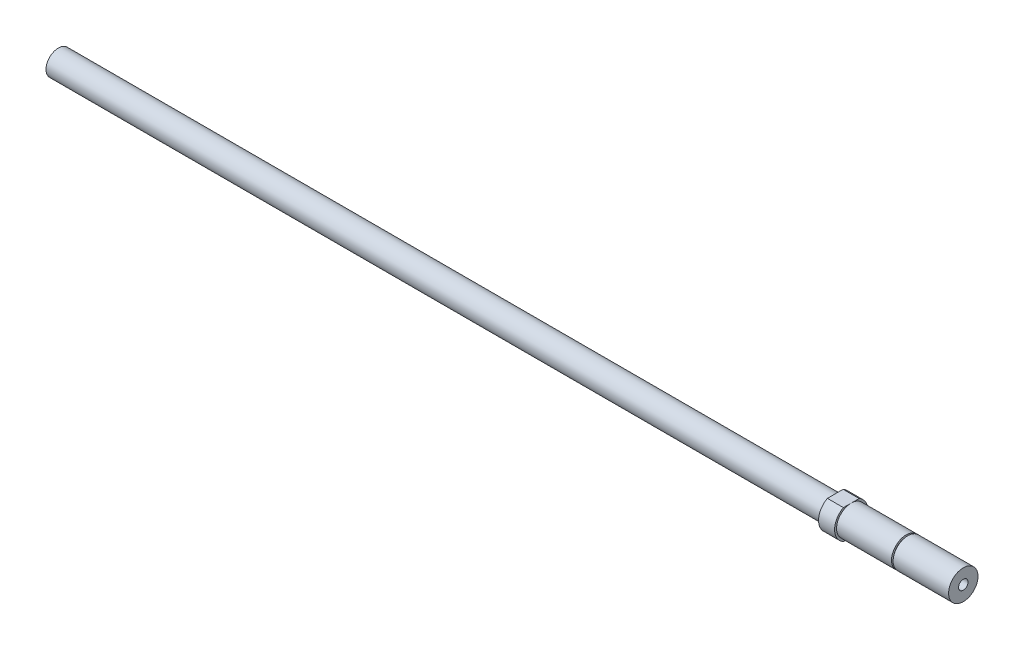
SolidWorks part; units mm, degrees
ref_plane "XY" through (0, 0, 0) normal (0, 0, 1) x (1, 0, 0)
ref_plane "XZ" through (0, 0, 0) normal (0, 1, 0) x (1, 0, 0)
ref_plane "YZ" through (0, 0, 0) normal (1, 0, 0) x (0, 0, -1)
ref_axis "X" through (-226.1616, 0, 0) along (1, 0, 0)
ref_axis "Y" through (0, -3.85, 0) along (0, 1, 0)
ref_axis "Z" through (0, 0, 4.3656) along (0, 0, -1)
sketch "Sketch1" plane through (0, 0, 0) normal (0, 0, 1) x (1, 0, 0)
  line L0 (0, 0) -> (-215.392, 0)
  line L1 (-215.392, 0) -> (-215.392, 2.95)
  line L2 (-215.392, 2.95) -> (-30.48, 2.95)
  line L3 (-30.48, 2.95) -> (-30.48, 3.9687)
  line L4 (-30.48, 3.9687) -> (-26.67, 3.9687)
  line L5 (-26.67, 3.9687) -> (-26.67, 3.5)
  line L6 (-26.67, 3.5) -> (-13.589, 3.5)
  line L7 (0, 3.5) -> (0, 0)
  line L8 (-13.589, 3.5) -> (-13.589, 3.0226)
  line L9 (-13.589, 3.0226) -> (-13.208, 3.0226)
  line L10 (-13.208, 3.0226) -> (-13.208, 3.5)
  line L11 (-13.208, 3.5) -> (0, 3.5)
  dimension "D1" = 184.912
  dimension "D2" = 3.81
  dimension "D3" = 13.081
  dimension "D4" = 2.95
  dimension "D5" = 3.9688
  dimension "D6" = 3.0226
  dimension "D7" = 0.381
  dimension "D8" = 30.48
  dimension "D9" = 3.5
revolve "Revolve1" add sketch "Sketch1" angle 360 about L0
sketch "Sketch2" plane through (0, 0, 0) normal (1, 0, 0) x (0, 0, -1)
  line L1 (-3.9687, -3.5) -> (3.9687, -3.5)
  line L2 (-3.9687, -3.5) -> (-3.9687, 3.5)
  line L3 (-3.9687, 3.5) -> (3.9687, 3.5)
  line L4 (3.9687, -3.5) -> (3.9687, 3.5)
  circle A0 centre (0, 0) radius 3.5 construction
  circle A1 centre (0, 0) radius 3.9688 construction
extrude "Cut-Extrude1" cut sketch "Sketch2" against normal through all flip side to cut
hole_wizard "#4-40 Tapped Hole1" positions "Sketch4" profile "Sketch6" tap size "#4-40" standard "ANSI Inch"
sketch "Sketch4" plane through (0, 0, 0) normal (1, 0, 0) x (0, 0, -1)
  point P0 (0, 0)
sketch "Sketch6" plane through (0, 0, 0) normal (0, 1, 0) x (0, 0, -1)
  line L0 (0, 0) -> (0, 8.2992)
  line L1 (0, 8.2992) -> (1.1303, 7.62)
  line L2 (1.1303, 7.62) -> (1.1303, 0)
  line L5 (1.1303, 0) -> (0, 0)
  line L10 (0, 8.2992) -> (-1.1303, 7.62) construction
  line L11 (0, -6.35) -> (0, 107.95) construction
  dimension "Tap Drill Dia." = 2.2606
  dimension "Tap Drill Depth" = 7.62
  dimension "Drill Angle" = 118
cosmetic thread "Hole Thread1" parameters "D1"=5.588, "D2"=2.8448
